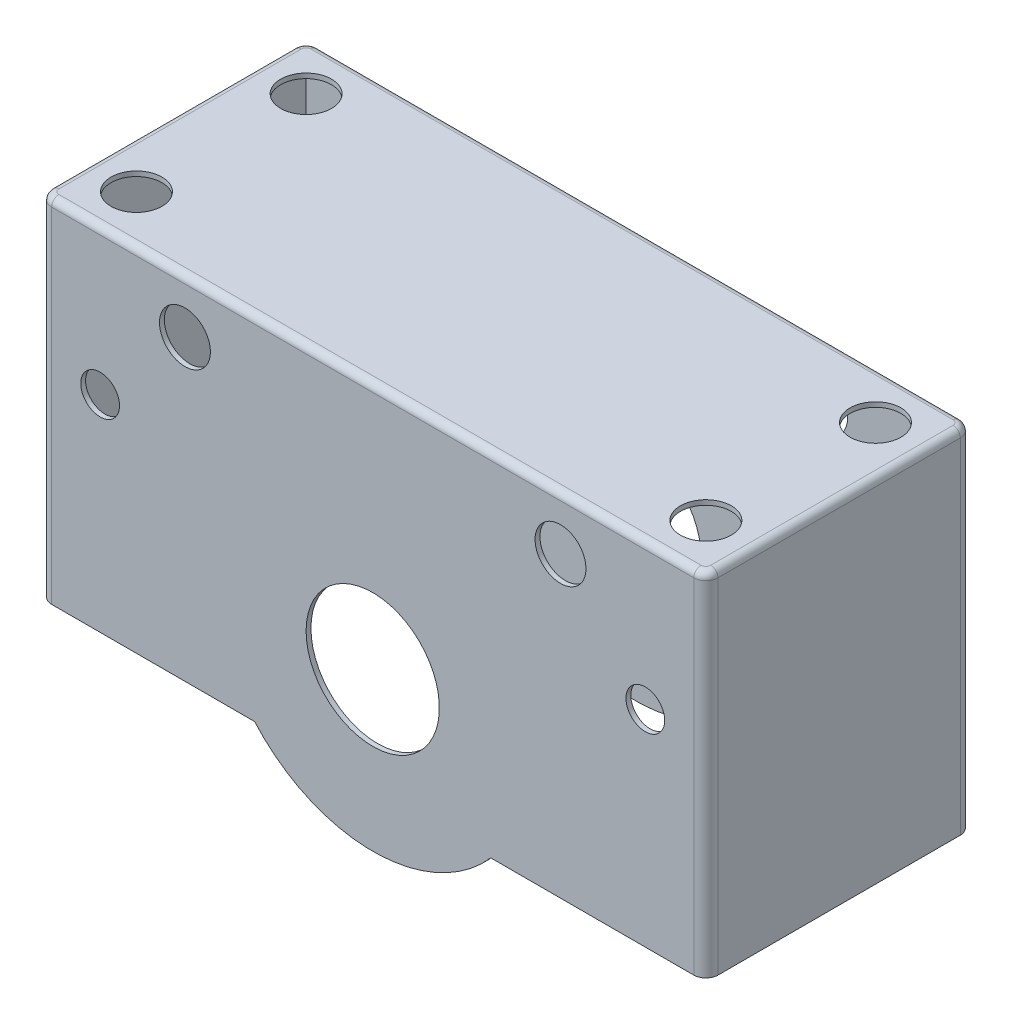
SolidWorks part; units mm, degrees
ref_plane "Plan de face" through (0, 0, 0) normal (0, 0, 1) x (1, 0, 0)
ref_plane "Plan de dessus" through (0, 0, 0) normal (0, 1, 0) x (1, 0, 0)
ref_plane "Plan de droite" through (0, 0, 0) normal (1, 0, 0) x (0, 0, -1)
sketch "Esquisse1" plane through (0, 0, 0) normal (0, 0, 1) x (1, 0, 0)
  line L0 (0, 106.6437) -> (0, 50.5) construction
  line L1 (-137.5, 72.5) -> (137.5, 72.5)
  line L2 (-137.5, 72.5) -> (-137.5, -72.5)
  line L4 (137.5, 72.5) -> (137.5, -72.5)
  line L5 (-137.5, 0) -> (137.5, 0) construction
  line L6 (-137.5, -72.5) -> (-48.7442, -72.5)
  line L7 (137.5, -72.5) -> (48.7442, -72.5)
  line L8 (0, 0) -> (0, -68.75) construction
  arc A0 (-48.7442, -72.5) -> (48.7442, -72.5) centre (0, -29.5) ccw
  point P7 (-137.5, 0)
  point P9 (0, 72.5)
  dimension "D3" = 130
  dimension "D1" = 275
  dimension "D2" = 102
  dimension "D4" = 145
extrude "Boss.-Extru.1" add sketch "Esquisse1" along normal mid plane 110
shell "Coque1" thickness 2 removed face at (-93.1221, -72.5, 0) removed face at (0, -83.5, 0) removed face at (93.1221, -72.5, 0)
ref_plane "Plan4" through (0, 0, -55) normal (0, 0, -1) x (-1, 0, 0)
sketch "Esquisse2" plane through (0, 0, -55) normal (0, 0, -1) x (-1, 0, 0)
  circle A0 centre (0, -29.5) radius 27.5
  arc A1 (-48.7442, -72.5) -> (48.7442, -72.5) centre (0, -29.5) ccw construction
  dimension "D1" = 55
extrude "Enlèv. mat.-Extru.1" cut sketch "Esquisse2" against normal through all
ref_plane "Plan5" through (0, 72.5, 0) normal (0, 1, 0) x (1, 0, 0)
sketch "Esquisse3" plane through (0, 72.5, 0) normal (0, 1, 0) x (1, 0, 0)
  line L0 (137.5, 55) -> (-137.5, 55) construction
  line L1 (-137.5, -55) -> (-137.5, 55) construction
  line L2 (137.5, -55) -> (-137.5, -55) construction
  line L3 (0, 0) -> (0, 53.6772) construction
  line L4 (91.85, 55) -> (-91.85, 55) construction
  line L5 (137.5, -55) -> (137.5, 55) construction
  circle A0 centre (-117.5, 35) radius 10.5
  circle A1 centre (-117.5, -35) radius 10.5
  circle A2 centre (117.5, 35) radius 10.5
  circle A3 centre (117.5, -35) radius 10.5
  dimension "D1" = 21
  dimension "D3" = 21
  dimension "D2" = 20
  dimension "13" = 20
  dimension "²" = 20
  dimension "D5" = 20
  dimension "137.5" = 137.5
extrude "Enlèv. mat.-Extru.2" cut sketch "Esquisse3" against normal through all
fillet "Congé2" radius 3 4 edges at (137.5, 72.5, 0) (0, 72.5, -55) (0, 72.5, 55) (-137.5, 72.5, 0)
fillet "Congé3" radius 5 8 edges at (-136.6213, 71.6213, 54.1213) (136.6213, 71.6213, 54.1213) (136.6213, 71.6213, -54.1213) (-136.6213, 71.6213, -54.1213) (-137.5, -1.5, -55) (137.5, -1.5, -55) (137.5, -1.5, 55) (-137.5, -1.5, 55)
ref_plane "Plan6" through (0, 0, -55) normal (0, 0, -1) x (-1, 0, 0)
sketch "Esquisse4" plane through (0, 0, -55) normal (0, 0, -1) x (-1, 0, 0)
  line L0 (-137.5, -72.5) -> (-137.5, 69.5) construction
  line L1 (137.5, 69.5) -> (137.5, -72.5) construction
  line L2 (57.2, 72.5) -> (-57.2, 72.5) construction
  circle A0 centre (-77.5, 50.5) radius 10.5
  circle A1 centre (77.5, 50.5) radius 10.5
  circle A2 centre (112.5, 12.5) radius 8
  circle A3 centre (-112.5, 12.5) radius 8
  point P8 (0, 0)
  point P15 (0, 0)
  point P16 (-112.5, 18.227)
  dimension "D1" = 21
  dimension "D2" = 21
  dimension "D7" = 16
  dimension "D8" = 16
  dimension "D3" = 60
  dimension "D4" = 60
  dimension "D5" = 22
  dimension "D6" = 22
  dimension "D9" = 25
  dimension "D10" = 25
  dimension "D11" = 60
  dimension "D12" = 60
extrude "Enlèv. mat.-Extru.3" cut sketch "Esquisse4" against normal through all
